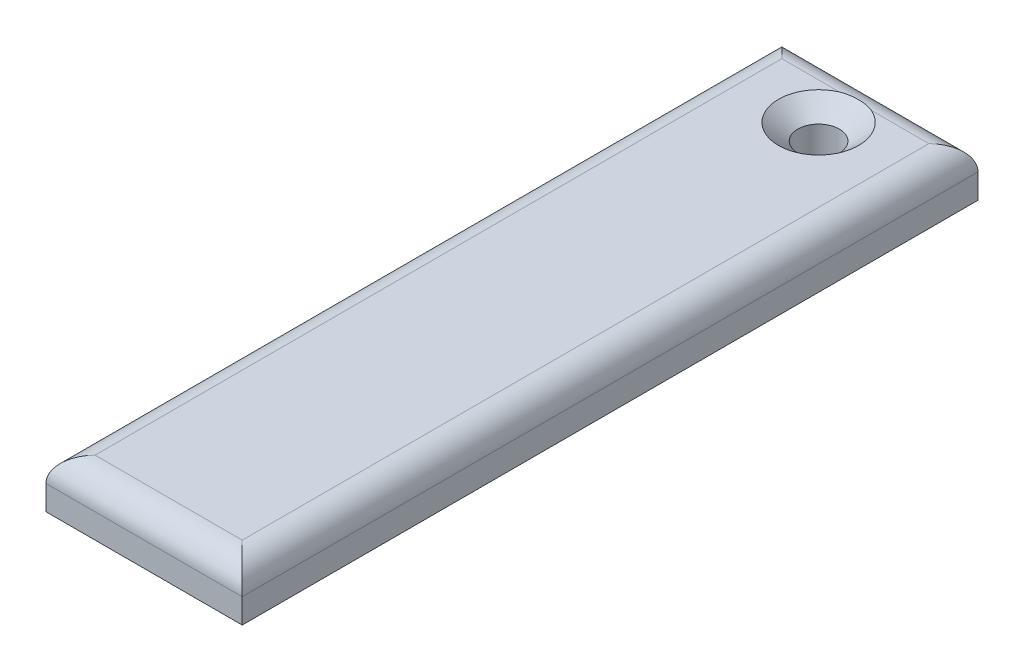
SolidWorks part; units mm, degrees
ref_plane "Front Plane" through (0, 0, 0) normal (0, 0, 1) x (1, 0, 0)
ref_plane "Top Plane" through (0, 0, 0) normal (0, 1, 0) x (1, 0, 0)
ref_plane "Right Plane" through (0, 0, 0) normal (1, 0, 0) x (0, 0, -1)
sketch "Sketch1" plane through (0, 0, 0) normal (0, 1, 0) x (1, 0, 0)
  line L1 (-10.16, -38.1) -> (10.16, -38.1)
  line L2 (-10.16, -38.1) -> (-10.16, 38.1)
  line L3 (-10.16, 38.1) -> (10.16, 38.1)
  line L4 (10.16, -38.1) -> (10.16, 38.1)
  line L5 (-10.16, -38.1) -> (10.16, 38.1) construction
  line L6 (-10.16, 38.1) -> (10.16, -38.1) construction
  point P0 (0, 0)
  dimension "D1" = 76.2
  dimension "D2" = 20.32
extrude "Boss-Extrude1" add sketch "Sketch1" along normal blind 5.08
hole_wizard "CSK for #6 Flat Head Machine Screw (100)1" positions "Sketch2" profile "Sketch3" countersink size "#6" standard "ANSI Inch" end condition through all
sketch "Sketch2" plane through (0, 5.08, 0) normal (0, 1, 0) x (1, 0, 0)
  line L0 (10.16, 38.1) -> (-10.16, 38.1) construction
  point P0 (0, 31.75)
  dimension "D1" = 6.35
sketch "Sketch3" plane through (0, 5.08, -31.75) normal (1, 0, 0) x (0, 0, 1)
  line L0 (0, 0) -> (0, 5.08)
  line L1 (0, 5.08) -> (2.1526, 5.08)
  line L2 (2.1526, 5.08) -> (2.1526, 1.6749)
  line L3 (2.1526, 1.6749) -> (4.1487, 0)
  line L5 (4.1487, 0) -> (0, 0)
  line L6 (-2.1527, 1.6749) -> (-4.1487, 0) construction
  line L11 (0, -6.35) -> (0, 107.95) construction
  dimension "Thru Hole Dia." = 4.3053
  dimension "Thru Hole Depth" = 5.08
  dimension "Near C'Sink Dia." = 8.2974
  dimension "Near C'Sink Angle" = 100
fillet "Fillet1" radius 2.54 4 edges at (0, 5.08, -38.1) (10.16, 5.08, 0) (-10.16, 5.08, 0) (0, 5.08, 38.1)
